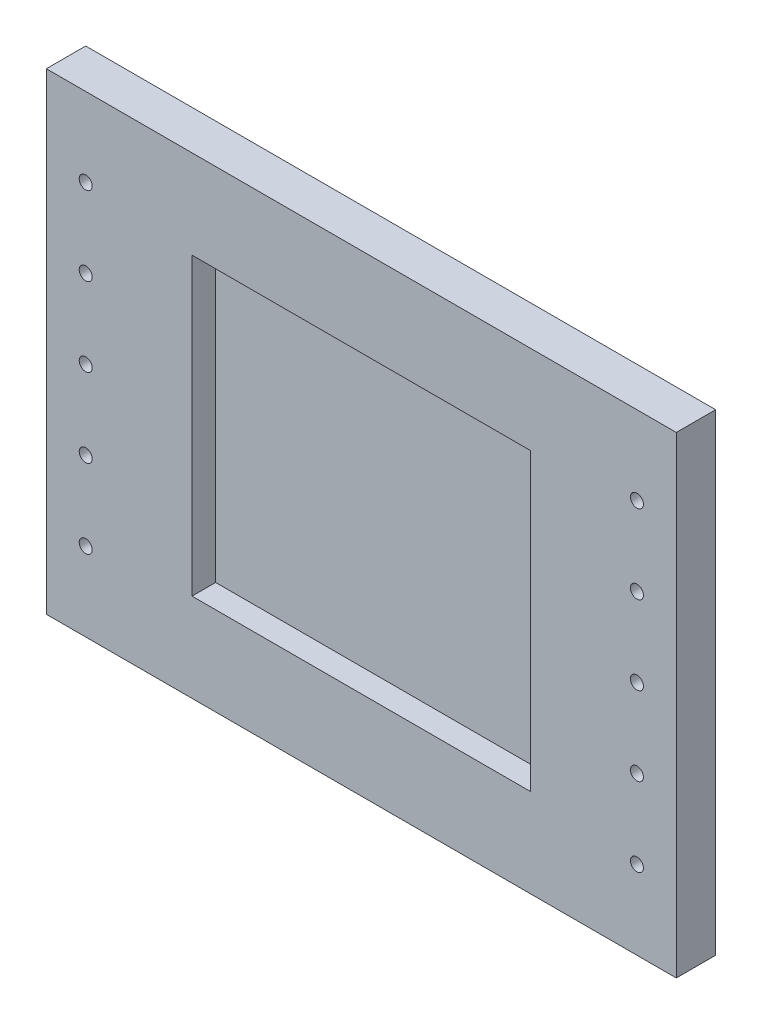
SolidWorks part; units mm, degrees
ref_plane "前视基准面" through (0, 0, 0) normal (0, 0, 1) x (1, 0, 0)
ref_plane "上视基准面" through (0, 0, 0) normal (0, 1, 0) x (1, 0, 0)
ref_plane "右视基准面" through (0, 0, 0) normal (1, 0, 0) x (0, 0, -1)
other "Configuration Table"
sketch "草图1" plane through (0, 0, 0) normal (0, 0, 1) x (1, 0, 0)
  line L1 (-80, 60) -> (80, 60)
  line L2 (-80, 60) -> (-80, -60)
  line L3 (-80, -60) -> (80, -60)
  line L4 (80, 60) -> (80, -60)
  line L5 (-80, 60) -> (80, -60) construction
  line L6 (-80, -60) -> (80, 60) construction
  point P0 (0, 0)
  dimension "D1" = 160
  dimension "D2" = 120
extrude "凸台-拉伸1" add sketch "草图1" along normal blind 10
sketch "草图2" plane through (0, 0, 10) normal (0, 0, 1) x (1, 0, 0)
  line L0 (-80, 0) -> (80, 0) construction
  line L1 (-80, 60) -> (-80, -60) construction
  line L2 (80, -60) -> (80, 60) construction
  line L3 (0, 60) -> (0, -60) construction
  line L4 (80, 60) -> (-80, 60) construction
  line L5 (-80, -60) -> (80, -60) construction
  line L7 (-43, 37.5) -> (43, 37.5)
  line L8 (-43, 37.5) -> (-43, -37.5)
  line L9 (-43, -37.5) -> (43, -37.5)
  line L10 (43, 37.5) -> (43, -37.5)
  line L11 (-43, 37.5) -> (43, -37.5) construction
  line L12 (-43, -37.5) -> (43, 37.5) construction
  point P12 (0, 0)
  dimension "D1" = 86
  dimension "D2" = 75
extrude "切除-拉伸1" cut sketch "草图2" against normal blind 6
sketch "草图3" plane through (0, 0, 0) normal (0, 0, -1) x (-1, 0, 0)
  line L0 (-80, -60) -> (-80, 60) construction
  line L1 (-80, 60) -> (80, 60) construction
  circle A0 centre (-70, 40) radius 1.65
  circle A1 centre (-70, 20) radius 1.65
  circle A2 centre (-70, 0) radius 1.65
  circle A3 centre (-70, -20) radius 1.65
  circle A4 centre (-70, -40) radius 1.65
  dimension "D1" = 3.3
  dimension "D2" = 10
  dimension "D3" = 20
  dimension "D4" = 5
extrude "切除-拉伸2" cut sketch "草图3" against normal through all
mirror "镜向1" about plane through (0, 0, 0) normal (1, 0, 0) of "切除-拉伸2"
